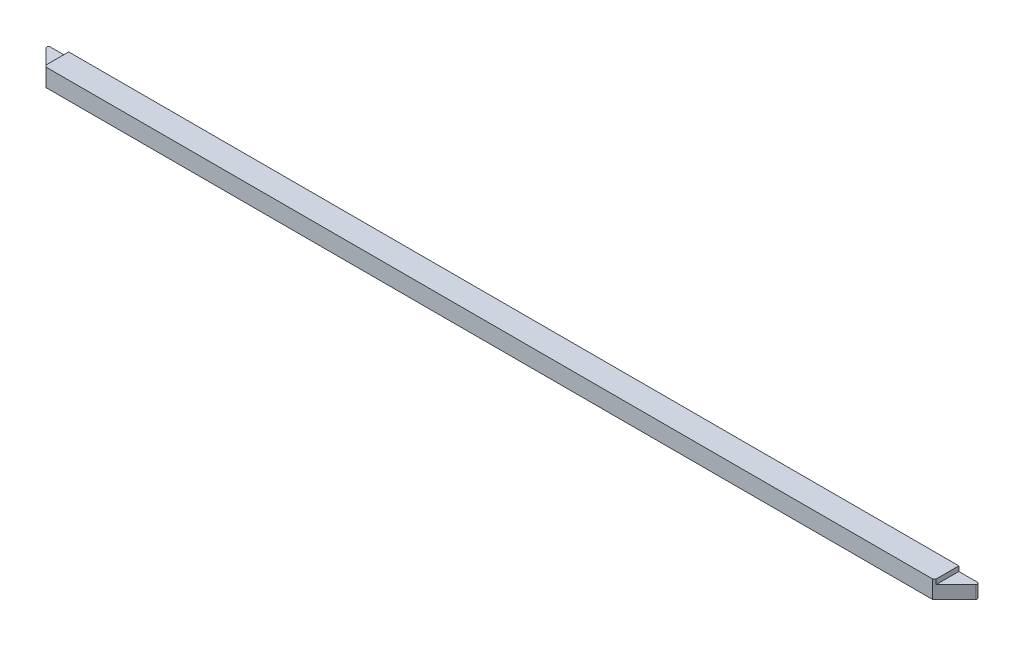
SolidWorks part; units mm, degrees
ref_plane "Plan de face" through (0, 0, 0) normal (0, 0, 1) x (1, 0, 0)
ref_plane "Plan de dessus" through (0, 0, 0) normal (0, 1, 0) x (1, 0, 0)
ref_plane "Plan de droite" through (0, 0, 0) normal (1, 0, 0) x (0, 0, -1)
sketch "Esquisse1" plane through (0, 0, 0) normal (0, 1, 0) x (1, 0, 0)
  line L7 (0, 0) -> (200, 0)
  line L8 (0, 0) -> (0, 5.5)
  line L9 (0, 5.5) -> (200, 5.5)
  line L10 (200, 0) -> (200, 5.5)
  dimension "D1" = 5.5
  dimension "D2" = 200
extrude "Boss.-Extru.1" add sketch "Esquisse1" along normal blind 4
chamfer "Chanfrein1" distance 0.4 angle 45 2 edges at (200, 2, 0) (0, 2, 0)
sketch "Esquisse2" plane through (0, 0, 0) normal (0, 1, 0) x (1, 0, 0)
  line L0 (0, 5.5) -> (-5.1, 5.5)
  line L1 (-5.1, 5.5) -> (0, 0.4)
  line L2 (0, 0.4) -> (0, 5.5)
  line L3 (0.4, 0) -> (0, 0.4) construction
extrude "Boss.-Extru.2" add sketch "Esquisse2" along normal offset from surface (2.9 mm away) 1.1 up to face at (100, 4, -1.9667)
ref_plane "Plan1" through (100, 0, 0) normal (-1, 0, 0) x (0, 0, 1)
mirror "Symétrie1" about plane through (100, 0, 0) normal (-1, 0, 0) of "Boss.-Extru.2"
fillet "Congé1" radius 0.4 2 edges at (205.1, 1.45, -5.5) (-5.1, 1.45, -5.5)
